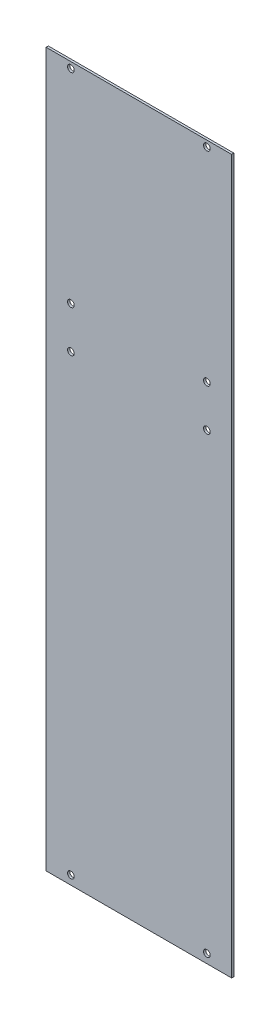
SolidWorks part; units mm, degrees
material "6061 Сплав"
ref_plane "Front Plane" through (0, 0, 0) normal (0, 0, 1) x (1, 0, 0)
ref_plane "Top Plane" through (0, 0, 0) normal (0, 1, 0) x (1, 0, 0)
ref_plane "Right Plane" through (0, 0, 0) normal (1, 0, 0) x (0, 0, -1)
sketch "Sketch1" plane through (0, 0, 0) normal (0, 0, 1) x (1, 0, 0)
  line L1 (41.6, -160) -> (-41.6, -160)
  line L2 (41.6, -160) -> (41.6, 160)
  line L3 (41.6, 160) -> (-41.6, 160)
  line L4 (-41.6, -160) -> (-41.6, 160)
  line L5 (41.6, -160) -> (-41.6, 160) construction
  line L6 (41.6, 160) -> (-41.6, -160) construction
  point P0 (0, 0)
  dimension "D1" = 83.2
  dimension "D2" = 320
extrude "Boss-Extrude1" add sketch "Sketch1" along normal blind 1
hole_wizard "Ø3.0 (3) Diameter Hole1" positions "Sketch3" profile "Sketch2" hole size "Ø3.0" standard "ANSI Metric"
sketch "Sketch3" plane through (0, 0, 1) normal (0, 0, 1) x (1, 0, 0)
  line L6 (-41.6, -160) -> (41.6, -160) construction
  line L9 (41.6, 160) -> (-41.6, 160) construction
  line L10 (0, 160) -> (0, 163.7587) construction
  line L11 (0, 160) -> (0, -152.1509) construction
  point P0 (-30.5, 66)
  point P2 (30.5, 66)
  point P15 (30.5, -156)
  point P17 (-30.5, -156)
  point P54 (-30.5, 157.3)
  point P56 (30.5, 157.3)
  point P58 (-30.5, 47.3)
  point P60 (30.5, 47.3)
  dimension "D2" = 4
  dimension "D3" = 2.7
  dimension "D4" = 4
  dimension "D5" = 30.5
  dimension "D6" = 30.5
  dimension "D7" = 94
  dimension "D8" = 30.5
  dimension "D9" = 2.7
  dimension "D10" = 94
  dimension "D11" = 30.5
  dimension "D12" = 30.5
  dimension "D13" = 30.5
  dimension "D14" = 30.5
  dimension "D15" = 30.5
  dimension "D16" = 112.7
  dimension "D17" = 112.7
sketch "Sketch2" plane through (-30.5, 66, 1) normal (1, 0, 0) x (0, -1, 0)
  line L0 (0, 0) -> (0, 1)
  line L1 (0, 1) -> (1.5, 1)
  line L2 (1.5, 1) -> (1.5, 0)
  line L5 (1.5, 0) -> (0, 0)
  line L10 (0, 1) -> (-1.5, 1) construction
  line L11 (0, -6.35) -> (0, 107.95) construction
  dimension "Hole Dia." = 3
  dimension "Hole Depth" = 1
  dimension "Drill Angle" = 180
